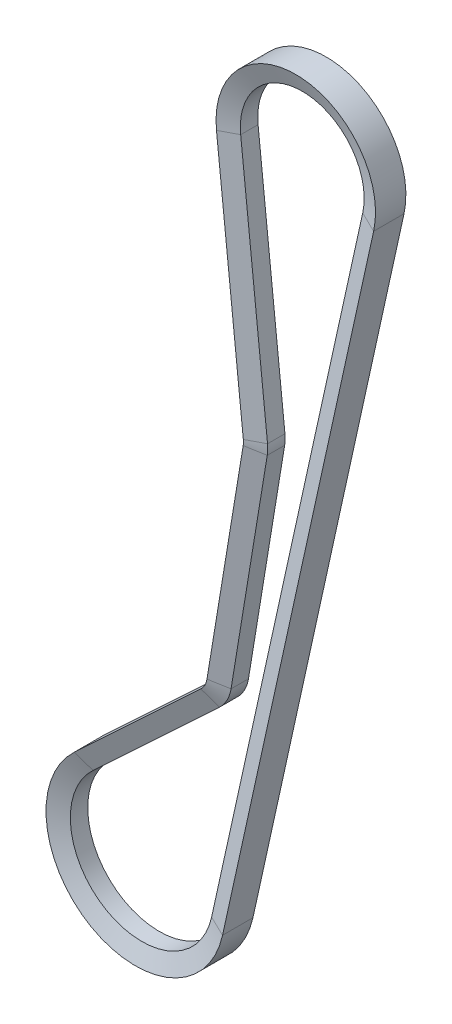
SolidWorks part; units mm, degrees
ref_plane "Front Plane" through (0, 0, 0) normal (0, 0, 1) x (1, 0, 0)
ref_plane "Top Plane" through (0, 0, 0) normal (0, 1, 0) x (1, 0, 0)
ref_plane "Right Plane" through (0, 0, 0) normal (1, 0, 0) x (0, 0, -1)
sketch "Sketch2" plane through (0, 0, 0) normal (0, 0, 1) x (1, 0, 0)
  line L0 (0, 0) -> (1, 0) construction
  line L1 (0, 0) -> (0, 1) construction
  line L12 (24.4135, -5.3833) -> (-22.9548, -220.2024)
  line L14 (-69.4026, -193.7033) -> (-29.7686, -156.7125)
  line L15 (-27.8352, -153.0996) -> (-16.4884, -84.0253)
  line L16 (-16.4395, -82.3287) -> (-24.8616, -2.6271)
  arc A4 (-22.9548, -220.2024) -> (-69.4026, -193.7033) centre (-50.298, -214.1731) cw
  arc A7 (-24.8616, -2.6271) -> (24.4135, -5.3833) centre (0, 0) cw
  arc A8 (-29.7686, -156.7125) -> (-27.8352, -153.0996) centre (-34.1012, -152.0703) ccw
  arc A9 (-16.4884, -84.0253) -> (-16.4395, -82.3287) centre (-22.7544, -82.996) ccw
ref_plane "Plane4" through (-24.8616, -2.6271, 0) normal (-0.1051, 0.9945, 0) x (0.9945, 0.1051, 0)
sketch "Sketch3" plane through (-24.8616, -2.6271, 0) normal (-0.1051, 0.9945, 0) x (0.9945, 0.1051, 0)
  line L0 (0, -4.7625) -> (0, 4.7625)
  line L1 (0, -4.7625) -> (5.588, -2.7286)
  line L2 (5.588, -2.7286) -> (5.588, 2.7286)
  line L3 (5.588, 2.7286) -> (0, 4.7625)
  line L4 (0, 0) -> (5.588, 0) construction
  dimension "D1" = 9.525
  dimension "D2" = 5.588
  dimension "D3" = 40
sweep "Sweep1" add profiles "Sketch3" path "Sketch2"
